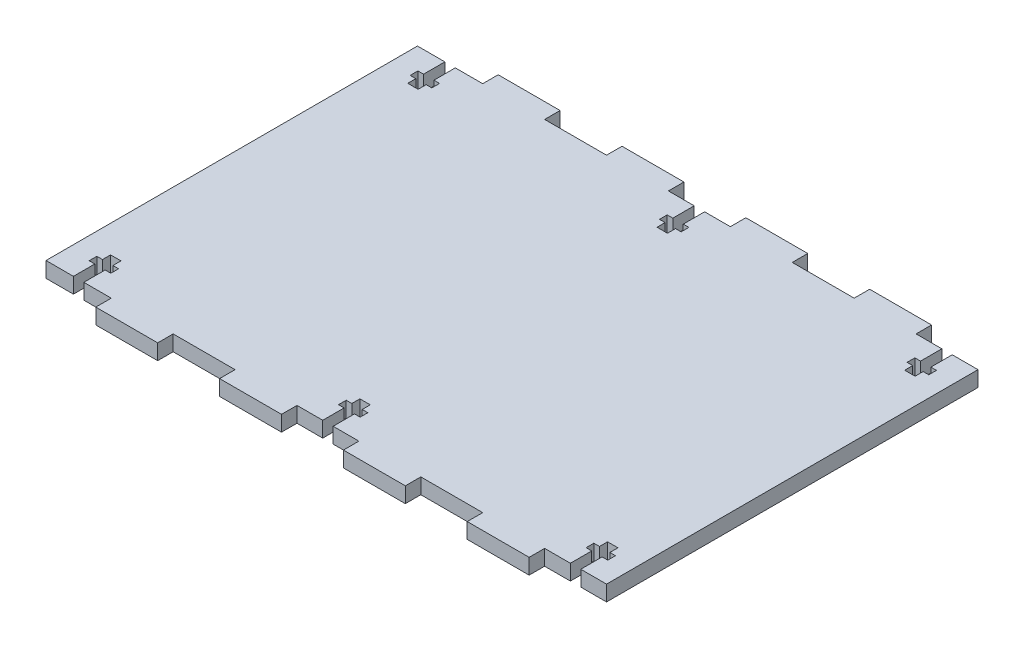
SolidWorks part; units mm, degrees
ref_plane "Front Plane" through (0, 0, 0) normal (0, 0, 1) x (1, 0, 0)
ref_plane "Top Plane" through (0, 0, 0) normal (0, 1, 0) x (1, 0, 0)
ref_plane "Right Plane" through (0, 0, 0) normal (1, 0, 0) x (0, 0, -1)
sketch "Sketch1" plane through (0, 0, 0) normal (0, 0, 1) x (1, 0, 0)
  line L0 (90.6195, -15.875) -> (90.6195, 155.575) construction
  line L1 (-139.3499, 155.575) -> (90.6195, 155.575)
  line L2 (-139.3499, 155.575) -> (-139.3499, 149.225)
  line L3 (-139.3499, 149.225) -> (90.6195, 149.225)
  line L4 (90.6195, 155.575) -> (90.6195, 149.225)
  dimension "D1" = 6.35
extrude "Boss-Extrude1" add sketch "Sketch1" along normal blind 152.4
sketch "Sketch2" plane through (0, 155.575, 0) normal (0, 1, 0) x (1, 0, 0)
  line L0 (65.2195, 0) -> (65.2195, 6.35)
  line L1 (90.6195, 0) -> (-139.3499, 0) construction
  line L2 (-139.3499, 6.35) -> (-112.5805, 6.35) construction
  line L3 (65.2195, 6.35) -> (39.8195, 6.35)
  line L4 (39.8195, 6.35) -> (39.8195, 0)
  line L5 (90.6195, 0) -> (65.2195, 0)
  line L6 (65.2195, 0) -> (39.8195, 0)
  line L9 (90.6195, 0) -> (-139.3499, 0)
  line L10 (-139.3499, 0) -> (-139.3499, -152.4)
  line L11 (-139.3499, -152.4) -> (90.6195, -152.4)
  line L12 (90.6195, -152.4) -> (90.6195, 0)
  line L13 (39.8195, 0) -> (-139.3499, 0)
  line L14 (-139.3499, 0) -> (-139.3499, -152.4)
  line L15 (-139.3499, -152.4) -> (90.6195, -152.4)
  line L16 (90.6195, -152.4) -> (90.6195, 0)
  line M7 (90.6195, 0) -> (-139.3499, 0)
  dimension "D1" = 25.4
  dimension "D2" = 25.4
  dimension "D3" = 0
extrude "Boss-Extrude2" add sketch "Sketch2" against normal blind 6.35 contours L3 L4 L0 M7 region at (52.5195, 155.575, -3.175)
pattern_linear "LPattern1" count 4 spacing 50.8 along (-1, 0, 0) of "Boss-Extrude2"
sketch "Sketch3" plane through (0, 0, 152.4) normal (0, 0, 1) x (1, 0, 0)
  line L0 (90.6195, 155.575) -> (-139.3499, 155.575) construction
  line L1 (65.2195, 155.575) -> (39.8195, 155.575)
  line L2 (65.2195, 155.575) -> (65.2195, 149.225)
  line L3 (65.2195, 149.225) -> (39.8195, 149.225)
  line L4 (39.8195, 155.575) -> (39.8195, 149.225)
  line L5 (-139.3499, 149.225) -> (90.6195, 149.225) construction
  dimension "D1" = 25.4
  dimension "D2" = 25.4
extrude "Boss-Extrude3" add sketch "Sketch3" along normal blind 6.35
pattern_linear "LPattern2" count 4 spacing 50.8 along (-1, 0, 0) of "Boss-Extrude3"
sketch "Sketch4" plane through (0, 155.575, 0) normal (0, 1, 0) x (1, 0, 0)
  line L0 (-139.3499, 0) -> (-112.5805, 0) construction
  line L1 (65.2195, 0) -> (90.6195, 0) construction
  line L2 (-125.9652, 0) -> (-125.9652, -13.6148) construction
  line L3 (-112.5805, 0) -> (-139.3499, 0) construction
  line L4 (-23.6805, 0) -> (-23.6805, -16.5479) construction
  line L5 (-10.9805, 0) -> (-36.3805, 0) construction
  line L6 (77.9195, 0) -> (77.9195, -21.5198) construction
  line L7 (90.6195, 0) -> (65.2195, 0) construction
  line L8 (77.9195, -152.4) -> (77.9195, -137.4626) construction
  line L9 (90.6195, -152.4) -> (65.2195, -152.4) construction
  line L10 (-23.6805, -152.4) -> (-23.6805, -137.4626) construction
  line L11 (-10.9805, -152.4) -> (-36.3805, -152.4) construction
  line L12 (-125.9652, -152.4) -> (-125.9652, -137.4626) construction
  line L13 (-112.5805, -152.4) -> (-139.3499, -152.4) construction
  line L14 (-139.3499, -152.4) -> (-112.5805, -152.4) construction
  line L15 (-36.3805, -152.4) -> (-10.9805, -152.4) construction
  line B0 (-123.8316, 0) -> (-128.0988, 0)
  line B1 (-128.0988, -11.938) -> (-130.4102, -11.938)
  line B2 (-130.4102, -11.938) -> (-130.4102, -8.763)
  line B3 (-130.4102, -8.763) -> (-128.0988, -8.763)
  line B4 (-128.0988, -8.763) -> (-128.0988, 0)
  line B5 (-128.0988, -11.938) -> (-128.0988, -15.24)
  line B6 (-128.0988, -15.24) -> (-123.8316, -15.24)
  line B7 (-123.8316, -11.938) -> (-123.8316, -15.24)
  line B8 (-123.8316, -8.763) -> (-123.8316, 0)
  line B9 (-121.5202, -8.763) -> (-123.8316, -8.763)
  line B10 (-121.5202, -11.938) -> (-121.5202, -8.763)
  line B11 (-123.8316, -11.938) -> (-121.5202, -11.938)
  line B12 (-21.5469, 0) -> (-25.8141, 0)
  line B13 (-25.8141, -11.938) -> (-28.1255, -11.938)
  line B14 (-28.1255, -11.938) -> (-28.1255, -8.763)
  line B15 (-28.1255, -8.763) -> (-25.8141, -8.763)
  line B16 (-25.8141, -8.763) -> (-25.8141, 0)
  line B17 (-25.8141, -11.938) -> (-25.8141, -15.24)
  line B18 (-25.8141, -15.24) -> (-21.5469, -15.24)
  line B19 (-21.5469, -11.938) -> (-21.5469, -15.24)
  line B20 (-21.5469, -8.763) -> (-21.5469, 0)
  line B21 (-19.2355, -8.763) -> (-21.5469, -8.763)
  line B22 (-19.2355, -11.938) -> (-19.2355, -8.763)
  line B23 (-21.5469, -11.938) -> (-19.2355, -11.938)
  line B24 (80.0531, 0) -> (75.7859, 0)
  line B25 (75.7859, -11.938) -> (73.4745, -11.938)
  line B26 (73.4745, -11.938) -> (73.4745, -8.763)
  line B27 (73.4745, -8.763) -> (75.7859, -8.763)
  line B28 (75.7859, -8.763) -> (75.7859, 0)
  line B29 (75.7859, -11.938) -> (75.7859, -15.24)
  line B30 (75.7859, -15.24) -> (80.0531, -15.24)
  line B31 (80.0531, -11.938) -> (80.0531, -15.24)
  line B32 (80.0531, -8.763) -> (80.0531, 0)
  line B33 (82.3645, -8.763) -> (80.0531, -8.763)
  line B34 (82.3645, -11.938) -> (82.3645, -8.763)
  line B35 (80.0531, -11.938) -> (82.3645, -11.938)
  line B36 (-128.0988, -152.4) -> (-123.8316, -152.4)
  line B37 (-123.8316, -140.462) -> (-121.5202, -140.462)
  line B38 (-121.5202, -140.462) -> (-121.5202, -143.637)
  line B39 (-121.5202, -143.637) -> (-123.8316, -143.637)
  line B40 (-123.8316, -143.637) -> (-123.8316, -152.4)
  line B41 (-123.8316, -140.462) -> (-123.8316, -137.16)
  line B42 (-123.8316, -137.16) -> (-128.0988, -137.16)
  line B43 (-128.0988, -140.462) -> (-128.0988, -137.16)
  line B44 (-128.0988, -143.637) -> (-128.0988, -152.4)
  line B45 (-130.4102, -143.637) -> (-128.0988, -143.637)
  line B46 (-130.4102, -140.462) -> (-130.4102, -143.637)
  line B47 (-128.0988, -140.462) -> (-130.4102, -140.462)
  line B48 (-25.8141, -152.4) -> (-21.5469, -152.4)
  line B49 (-21.5469, -140.462) -> (-19.2355, -140.462)
  line B50 (-19.2355, -140.462) -> (-19.2355, -143.637)
  line B51 (-19.2355, -143.637) -> (-21.5469, -143.637)
  line B52 (-21.5469, -143.637) -> (-21.5469, -152.4)
  line B53 (-21.5469, -140.462) -> (-21.5469, -137.16)
  line B54 (-21.5469, -137.16) -> (-25.8141, -137.16)
  line B55 (-25.8141, -140.462) -> (-25.8141, -137.16)
  line B56 (-25.8141, -143.637) -> (-25.8141, -152.4)
  line B57 (-28.1255, -143.637) -> (-25.8141, -143.637)
  line B58 (-28.1255, -140.462) -> (-28.1255, -143.637)
  line B59 (-25.8141, -140.462) -> (-28.1255, -140.462)
  line B60 (75.7859, -152.4) -> (80.0531, -152.4)
  line B61 (80.0531, -140.462) -> (82.3645, -140.462)
  line B62 (82.3645, -140.462) -> (82.3645, -143.637)
  line B63 (82.3645, -143.637) -> (80.0531, -143.637)
  line B64 (80.0531, -143.637) -> (80.0531, -152.4)
  line B65 (80.0531, -140.462) -> (80.0531, -137.16)
  line B66 (80.0531, -137.16) -> (75.7859, -137.16)
  line B67 (75.7859, -140.462) -> (75.7859, -137.16)
  line B68 (75.7859, -143.637) -> (75.7859, -152.4)
  line B69 (73.4745, -143.637) -> (75.7859, -143.637)
  line B70 (73.4745, -140.462) -> (73.4745, -143.637)
  line B71 (75.7859, -140.462) -> (73.4745, -140.462)
sketch_block_instance "TSlot-1"
sketch_block "TSlot" parameters "D1"=3.302, "D2"=3.175
sketch_block_instance "TSlot-3"
sketch_block_instance "TSlot-4"
sketch_block_instance "TSlot-9"
sketch_block_instance "TSlot-11"
sketch_block_instance "TSlot-12"
extrude "Cut-Extrude1" cut sketch "Sketch4" against normal blind 6.35
